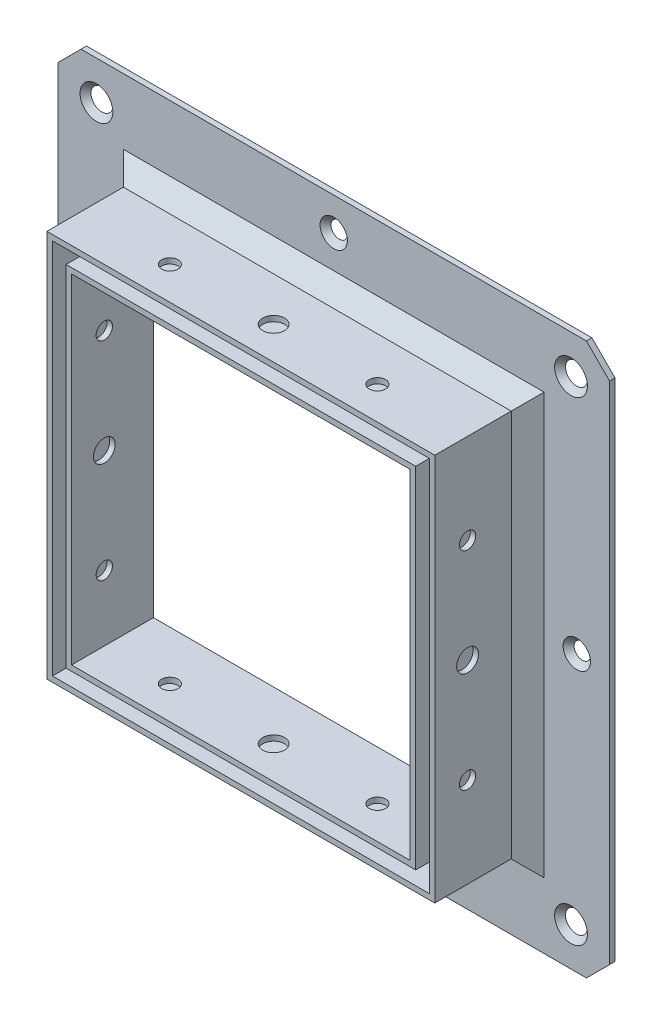
SolidWorks part; units mm, degrees
ref_plane "Ön Düzlem" through (0, 0, 0) normal (0, 0, 1) x (1, 0, 0)
ref_plane "Üst Düzlem" through (0, 0, 0) normal (0, 1, 0) x (1, 0, 0)
ref_plane "Sağ Düzlem" through (0, 0, 0) normal (1, 0, 0) x (0, 0, -1)
sketch "Çizim1" plane through (0, 0, 0) normal (0, 0, 1) x (1, 0, 0)
  line L0 (0, 0) -> (0, -68.4372) construction
  line L1 (0, 0) -> (90.2214, 0) construction
  line L3 (-35.5, 35.5) -> (35.5, 35.5)
  line L4 (-35.5, 35.5) -> (-35.5, -35.5)
  line L5 (-35.5, -35.5) -> (35.5, -35.5)
  line L6 (35.5, 35.5) -> (35.5, -35.5)
  line L7 (-31, 31) -> (31, 31)
  line L8 (-31, 31) -> (-31, -31)
  line L9 (-31, -31) -> (31, -31)
  line L10 (31, 31) -> (31, -31)
  line L11 (-34.5, 34.5) -> (34.5, 34.5)
  line L12 (-34.5, 34.5) -> (-34.5, -34.5)
  line L13 (-34.5, -34.5) -> (34.5, -34.5)
  line L14 (34.5, 34.5) -> (34.5, -34.5)
  line L15 (-32, 32) -> (32, 32)
  line L16 (-32, 32) -> (-32, -32)
  line L17 (-32, -32) -> (32, -32)
  line L18 (32, 32) -> (32, -32)
  dimension "D2" = 32
  dimension "D3" = 32
  dimension "D4" = 1
  dimension "D5" = 69
  dimension "D6" = 69
  dimension "D7" = 64
  dimension "D8" = 64
  dimension "D9" = 2.5
  dimension "D10" = 2.5
  dimension "D11" = 1
  dimension "D12" = 1
  dimension "D13" = 1
  dimension "D14" = 1
  dimension "D15" = 1
  dimension "D16" = 1
  dimension "D17" = 1
extrude "Yükseklik-Ekstrüzyon1" add sketch "Çizim1" along normal blind 12 contours L18 L15 L16 L17 L7 L10 L9 L8 | L6 L3 L4 L5 L11 L14 L13 L12 region at (0, 35.3996, 0) region at (0, 31.0949, 0)
sketch "Çizim3" plane through (0, 0, 0) normal (0, 0, -1) x (-1, 0, 0)
  line L1 (-35.5, 35.5) -> (35.5, 35.5)
  line L2 (-35.5, 35.5) -> (-35.5, -35.5)
  line L3 (-35.5, -35.5) -> (35.5, -35.5)
  line L4 (35.5, 35.5) -> (35.5, -35.5)
  line L5 (-31, 31) -> (31, 31)
  line L6 (-31, 31) -> (-31, -31)
  line L7 (-31, -31) -> (31, -31)
  line L8 (31, 31) -> (31, -31)
extrude "Yükseklik-Ekstrüzyon3" add sketch "Çizim3" along normal blind 5
sketch "Çizim4" plane through (0, 0, -5) normal (0, 0, -1) x (-1, 0, 0)
  line L0 (35.5, -35.5) -> (35.5, 35.5) construction
  line L1 (-50.5, 50.5) -> (50.5, 50.5)
  line L2 (-50.5, 50.5) -> (-50.5, -50.5)
  line L3 (-50.5, -50.5) -> (50.5, -50.5)
  line L4 (50.5, 50.5) -> (50.5, -50.5)
  line L5 (35.5, 35.5) -> (-35.5, 35.5) construction
  line L6 (-35.5, -35.5) -> (35.5, -35.5) construction
  line L7 (-35.5, 35.5) -> (-35.5, -35.5) construction
  line L9 (-31, 31) -> (31, 31)
  line L10 (-31, 31) -> (-31, -31)
  line L11 (-31, -31) -> (31, -31)
  line L12 (31, 31) -> (31, -31)
  dimension "D1" = 15
  dimension "D2" = 15
  dimension "D3" = 15
  dimension "D4" = 15
extrude "Yükseklik-Ekstrüzyon6" add sketch "Çizim4" along normal blind 1
chamfer "Pah1" distance 3 angle 45 4 edges at (0, 35.5, -5) (35.5, 0, -5) (0, -35.5, -5) (-35.5, 0, -5)
chamfer "Pah2" distance 3 angle 45 4 edges at (0, 31, -6) (-31, 0, -6) (0, -31, -6) (31, 0, -6)
sketch "Çizim6" plane through (0, 0, -6) normal (0, 0, -1) x (-1, 0, 0)
  line L0 (-50.5, -50.5) -> (-46.2574, -50.5)
  line L1 (-50.5, -50.5) -> (50.5, -50.5) construction
  line L2 (-46.2574, -50.5) -> (-50.5, -46.2574)
  line L3 (-50.5, 50.5) -> (-50.5, -50.5) construction
  line L4 (-50.5, -46.2574) -> (-50.5, -50.5)
  line L5 (-50.5, 50.5) -> (-50.5, 46.2574)
  line L6 (-50.5, 46.2574) -> (-46.2574, 50.5)
  line L7 (-46.2574, 50.5) -> (-50.5, 50.5)
  line L8 (50.5, 50.5) -> (46.2574, 50.5)
  line L9 (46.2574, 50.5) -> (50.5, 46.2574)
  line L10 (50.5, 46.2574) -> (50.5, 50.5)
  line L11 (50.5, -50.5) -> (50.5, -46.2574)
  line L12 (50.5, -46.2574) -> (46.2574, -50.5)
  line L13 (46.2574, -50.5) -> (50.5, -50.5)
  point P20 (0, 0)
  dimension "D1" = 6
  dimension "D2" = 4
extrude "Kes-Ekstrüzyon2" cut sketch "Çizim6" against normal blind 11
sketch "Çizim7" plane through (0, 0, -5) normal (0, 0, 1) x (1, 0, 0)
  line L0 (44.5, 23.1474) -> (44.5, -12.3252) construction
  line L1 (-44.5, 23.1474) -> (-44.5, -14.7302) construction
  line L2 (-18.7584, 44.5) -> (20.2014, 44.5) construction
  line L3 (-16.8345, -44.5) -> (24.7707, -44.5) construction
  line L4 (-38.5, 38.5) -> (-48.3787, 48.3787) construction
  line L5 (-46.2574, 50.5) -> (-50.5, 46.2574) construction
  circle A0 centre (-44.5, 0) radius 1.5
  circle A1 centre (0, 44.5) radius 1.5
  circle A2 centre (44.5, 0) radius 1.5
  circle A3 centre (0, -44.5) radius 1.5
  circle A4 centre (-43.4393, 43.4393) radius 2
  circle A5 centre (43.4393, 43.4393) radius 2
  circle A6 centre (43.4393, -43.4393) radius 2
  circle A7 centre (-43.4393, -43.4393) radius 2
  point P26 (0, 0)
  point P33 (0, 0)
  dimension "D5" = 3
  dimension "D1" = 4
  dimension "D2" = 4
  dimension "D6" = 4
extrude "Kes-Ekstrüzyon5" cut sketch "Çizim7" against normal blind 11
chamfer "Pah4" distance 1 angle 45 8 edges at (-43, 0, -5) (-41.4393, -43.4393, -5) (1.5, -44.5, -5) (45.4393, -43.4393, -5) (46, 0, -5) (45.4393, 43.4393, -5) (1.5, 44.5, -5) (-41.4393, 43.4393, -5)
sketch "Çizim8" plane through (35.5, 0, 0) normal (1, 0, 0) x (0, 0, -1)
  line L0 (-6, 24.1494) -> (-6, -21.3437) construction
  line L2 (0, 0) -> (-41.8937, 0) construction
  circle A0 centre (-6, 0) radius 2
  circle A1 centre (-6, 19) radius 1.5
  circle A2 centre (-6, -19) radius 1.5
  dimension "D1" = 4
  dimension "D2" = 3
  dimension "D3" = 19
extrude "Kes-Ekstrüzyon7" cut sketch "Çizim8" against normal blind 91
sketch "Çizim9" plane through (0, 35.5, 0) normal (0, 1, 0) x (1, 0, 0)
  line L0 (30.8176, -6) -> (-20.287, -6) construction
  line L2 (0, 0) -> (0, -22.745) construction
  circle A3 centre (0, -6) radius 2
  circle A4 centre (-19, -6) radius 1.5
  circle A5 centre (19, -6) radius 1.5
  dimension "D1" = 4
  dimension "D3" = 3
  dimension "D4" = 19
extrude "Kes-Ekstrüzyon9" cut sketch "Çizim9" against normal blind 91
